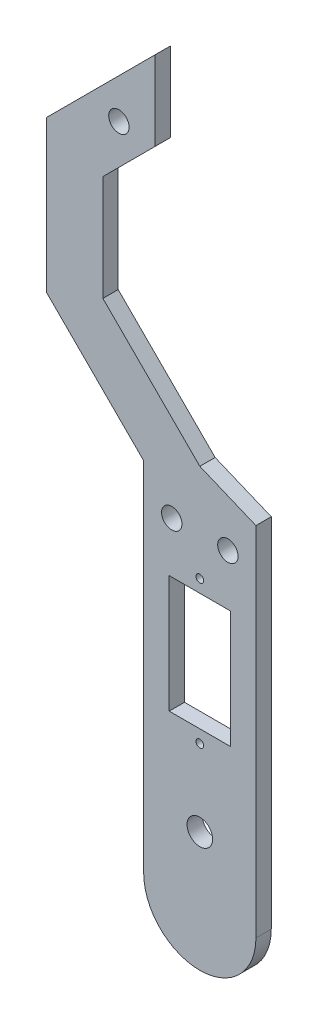
SolidWorks part; units mm, degrees
ref_plane "Front Plane" through (0, 0, 0) normal (0, 0, 1) x (1, 0, 0)
ref_plane "Top Plane" through (0, 0, 0) normal (0, 1, 0) x (1, 0, 0)
ref_plane "Right Plane" through (0, 0, 0) normal (1, 0, 0) x (0, 0, -1)
sketch "Croquis1" plane through (0, 0, 0) normal (0, 0, 1) x (1, 0, 0)
  line L1 (22, 0) -> (22, 70)
  line L2 (0, 0) -> (0, 70)
  line L3 (11, 0) -> (11, 74.5563) construction
  line L4 (0, 70) -> (-19, 89)
  line L5 (-19, 89) -> (-19, 118.7868)
  line L6 (-19, 118.7868) -> (2.2132, 140)
  line L7 (11, 74.5563) -> (-8, 93.5563)
  line L8 (-8, 93.5563) -> (-8, 114.2304)
  line L9 (2.2132, 140) -> (2.2132, 124.4437)
  line L10 (-8, 103.8934) -> (-19, 103.8934) construction
  line L11 (2.2132, 124.4437) -> (-8, 114.2304)
  line L12 (11, 74.5563) -> (22, 70)
  line L13 (22, 35) -> (0, 35) construction
  line L14 (-4.8579, 125.1508) -> (2.2132, 132.2218) construction
  line L15 (5, 53) -> (17, 53)
  line L16 (5, 53) -> (5, 30)
  line L17 (5, 30) -> (17, 30)
  line L18 (17, 53) -> (17, 30)
  circle A2 centre (5.5, 63) radius 2
  circle A3 centre (16.5, 63) radius 2
  circle A4 centre (-4.8579, 125.1508) radius 2
  circle A5 centre (11, 55.5) radius 0.75
  circle A6 centre (11, 27.5) radius 0.75
  arc A7 (0, 0) -> (22, 0) centre (11, 0) ccw
  circle A9 centre (11, 12.5) radius 2.5
  point P33 (11, 30)
  point P34 (11, 53)
  dimension "D8" = 11
  dimension "D14" = 1.5
  dimension "D15" = 1.5
  dimension "D20" = 4
  dimension "D21" = 4
  dimension "D24" = 17.5
  dimension "D23" = 5
  dimension "D1" = 22
  dimension "D2" = 70
  dimension "D3" = 45
  dimension "D4" = 30
  dimension "D5" = 11
  dimension "D6" = 70
  dimension "D7" = 30
  dimension "D9" = 5.5
  dimension "D10" = 11
  dimension "D11" = 10
  dimension "D12" = 23
  dimension "D13" = 12
  dimension "D16" = 2.5
  dimension "D17" = 2.5
  dimension "D18" = 7.5
  dimension "D19" = 5.5
  dimension "D22" = 30
extrude "Saliente-Extruir1" add sketch "Croquis1" along normal blind 3 contours L1 L12 L7 L8 L11 L9 L6 L5 L4 L2 A7
extrude "Cortar-Extruir1" cut sketch "Croquis1<4>" along normal through all and the other way blind 11 contours A2 | A3
sketch "Croquis1<4>" plane through (0, 0, 0) normal (0, 0, 1) x (1, 0, 0) same geometry as "Croquis1"
extrude "Cortar-Extruir3" cut sketch "Croquis1<5>" along normal through all contours A4
sketch "Croquis1<5>" plane through (0, 0, 0) normal (0, 0, 1) x (1, 0, 0) same geometry as "Croquis1"
extrude "TAMAÑO DEL SERVO" cut sketch "Croquis1<6>" along normal through all contours L18 L17 L16 L15
sketch "Croquis1<6>" plane through (0, 0, 0) normal (0, 0, 1) x (1, 0, 0) same geometry as "Croquis1"
extrude "Cortar-Extruir4" cut sketch "Croquis1<7>" along normal through all contours A5
sketch "Croquis1<7>" plane through (0, 0, 0) normal (0, 0, 1) x (1, 0, 0) same geometry as "Croquis1"
extrude "Cortar-Extruir5" cut sketch "Croquis1<8>" along normal through all contours A6
sketch "Croquis1<8>" plane through (0, 0, 0) normal (0, 0, 1) x (1, 0, 0) same geometry as "Croquis1"
sketch "Croquis2" plane through (0, 0, 3) normal (0, 0, 1) x (1, 0, 0)
extrude "Cortar-Extruir8" cut sketch "Croquis1<11>" along normal through all contours A9
sketch "Croquis1<11>" plane through (0, 0, 0) normal (0, 0, 1) x (1, 0, 0) same geometry as "Croquis1"
